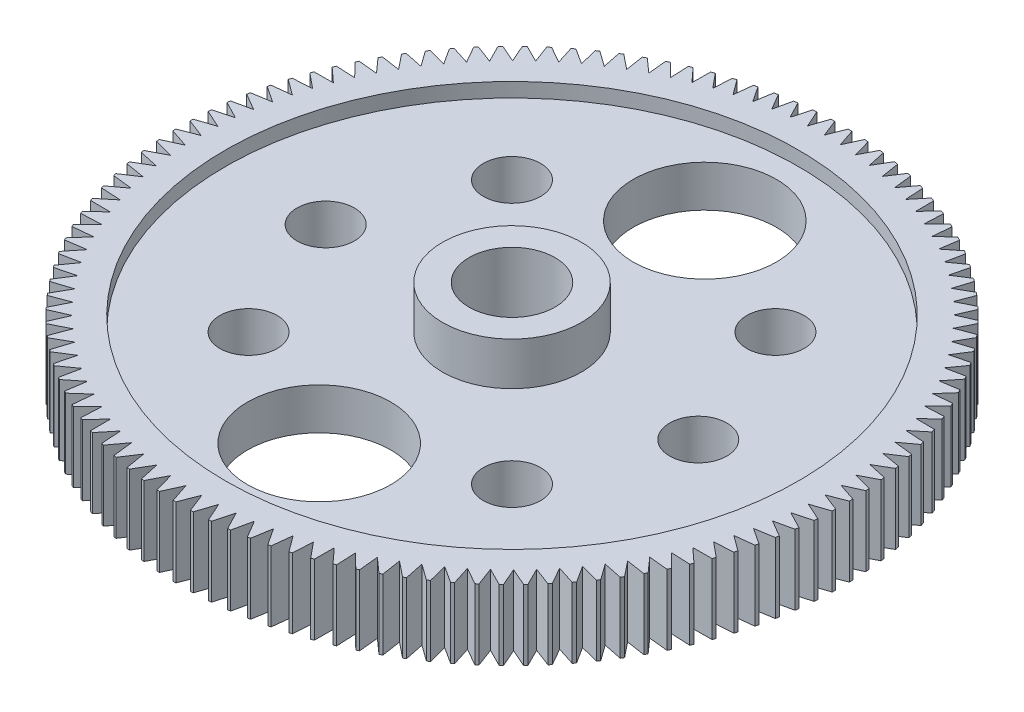
SolidWorks part; units mm, degrees
ref_plane "Спереди" through (0, 0, 0) normal (0, 0, 1) x (1, 0, 0)
ref_plane "Сверху" through (0, 0, 0) normal (0, 1, 0) x (1, 0, 0)
ref_plane "Справа" through (0, 0, 0) normal (1, 0, 0) x (0, 0, -1)
sketch "Эскиз1" plane through (0, 0, 0) normal (0, 1, 0) x (1, 0, 0)
  circle A0 centre (0, 0) radius 23
extrude "Вытянуть1" add sketch "Эскиз1" along normal blind 4.9
sketch "Эскиз2" plane through (0, 4.9, 0) normal (0, 1, 0) x (1, 0, 0)
  line L0 (0, 23) -> (0, 18.1182) construction
  line L1 (-0.5465, 23.1974) -> (0.5465, 23.1974)
  line L2 (0.5465, 23.1974) -> (0, 21.8005)
  line L3 (-0.5465, 23.1974) -> (0, 21.8005)
  line L4 (0.6655, 23.1956) -> (1.757, 23.1384)
  line L5 (1.757, 23.1384) -> (1.1382, 21.772)
  line L6 (0.6655, 23.1956) -> (1.1382, 21.772)
  line L7 (1.8758, 23.1302) -> (2.9628, 23.016)
  line L8 (2.9628, 23.016) -> (2.2733, 21.6839)
  line L9 (1.8758, 23.1302) -> (2.2733, 21.6839)
  line L10 (3.081, 23.0017) -> (4.1605, 22.8307)
  line L11 (4.1605, 22.8307) -> (3.4022, 21.5365)
  line L12 (3.081, 23.0017) -> (3.4022, 21.5365)
  line L13 (4.2778, 22.8102) -> (5.3469, 22.583)
  line L14 (5.3469, 22.583) -> (4.5219, 21.3302)
  line L15 (4.2778, 22.8102) -> (4.5219, 21.3302)
  line L16 (5.463, 22.5564) -> (6.5187, 22.2735)
  line L17 (6.5187, 22.2735) -> (5.6293, 21.0656)
  line L18 (5.463, 22.5564) -> (5.6293, 21.0656)
  line L19 (6.6332, 22.2409) -> (7.6727, 21.9031)
  line L20 (7.6727, 21.9031) -> (6.7213, 20.7434)
  line L21 (6.6332, 22.2409) -> (6.7213, 20.7434)
  line L22 (7.7853, 21.8645) -> (8.8057, 21.4728)
  line L23 (8.8057, 21.4728) -> (7.7949, 20.3646)
  line L24 (7.7853, 21.8645) -> (7.7949, 20.3646)
  line L25 (8.9162, 21.4284) -> (9.9147, 20.9838)
  line L26 (9.9147, 20.9838) -> (8.8473, 19.93)
  line L27 (8.9162, 21.4284) -> (8.8473, 19.93)
  line L28 (10.0227, 20.9337) -> (10.9965, 20.4375)
  line L29 (10.9965, 20.4375) -> (9.8754, 19.441)
  line L30 (10.0227, 20.9337) -> (9.8754, 19.441)
  line L31 (11.1017, 20.3818) -> (12.0483, 19.8353)
  line L32 (12.0483, 19.8353) -> (10.8766, 18.8988)
  line L33 (11.1017, 20.3818) -> (10.8766, 18.8988)
  line L34 (12.1504, 19.7741) -> (13.0671, 19.1788)
  line L35 (13.0671, 19.1788) -> (11.848, 18.3049)
  line L36 (12.1504, 19.7741) -> (11.848, 18.3049)
  line L37 (13.1659, 19.1124) -> (14.0502, 18.47)
  line L38 (14.0502, 18.47) -> (12.787, 17.6611)
  line L39 (13.1659, 19.1124) -> (12.787, 17.6611)
  line L40 (14.1453, 18.3985) -> (14.9948, 17.7106)
  line L41 (14.9948, 17.7106) -> (13.691, 16.969)
  line L42 (14.1453, 18.3985) -> (13.691, 16.969)
  line L43 (15.0861, 17.6343) -> (15.8984, 16.9029)
  line L44 (15.8984, 16.9029) -> (14.5575, 16.2305)
  line L45 (15.0861, 17.6343) -> (14.5575, 16.2305)
  line L46 (15.9855, 16.8219) -> (16.7584, 16.049)
  line L47 (16.7584, 16.049) -> (15.3842, 15.4477)
  line L48 (15.9855, 16.8219) -> (15.3842, 15.4477)
  line L49 (16.8412, 15.9635) -> (17.5726, 15.1512)
  line L50 (17.5726, 15.1512) -> (16.1688, 14.6227)
  line L51 (16.8412, 15.9635) -> (16.1688, 14.6227)
  line L52 (17.6508, 15.0615) -> (18.3387, 14.2121)
  line L53 (18.3387, 14.2121) -> (16.9092, 13.7577)
  line L54 (17.6508, 15.0615) -> (16.9092, 13.7577)
  line L55 (18.4121, 14.1184) -> (19.0546, 13.2341)
  line L56 (19.0546, 13.2341) -> (17.6032, 12.8552)
  line L57 (18.4121, 14.1184) -> (17.6032, 12.8552)
  line L58 (19.123, 13.1367) -> (19.7183, 12.2201)
  line L59 (19.7183, 12.2201) -> (18.2491, 11.9176)
  line L60 (19.123, 13.1367) -> (18.2491, 11.9176)
  line L61 (19.7816, 12.1192) -> (20.3281, 11.1726)
  line L62 (20.3281, 11.1726) -> (18.8451, 10.9475)
  line L63 (19.7816, 12.1192) -> (18.8451, 10.9475)
  line L64 (20.3859, 11.0686) -> (20.8822, 10.0947)
  line L65 (20.8822, 10.0947) -> (19.3894, 9.9475)
  line L66 (20.3859, 11.0686) -> (19.3894, 9.9475)
  line L67 (20.9345, 9.9878) -> (21.3791, 8.9893)
  line L68 (21.3791, 8.9893) -> (19.8807, 8.9204)
  line L69 (20.9345, 9.9878) -> (19.8807, 8.9204)
  line L70 (21.4258, 8.8798) -> (21.8175, 7.8594)
  line L71 (21.8175, 7.8594) -> (20.3175, 7.869)
  line L72 (21.4258, 8.8798) -> (20.3175, 7.869)
  line L73 (21.8584, 7.7476) -> (22.1961, 6.7081)
  line L74 (22.1961, 6.7081) -> (20.6987, 6.7962)
  line L75 (21.8584, 7.7476) -> (20.6987, 6.7962)
  line L76 (22.2311, 6.5943) -> (22.514, 5.5386)
  line L77 (22.514, 5.5386) -> (21.0233, 5.7049)
  line L78 (22.2311, 6.5943) -> (21.0233, 5.7049)
  line L79 (22.543, 5.4231) -> (22.7702, 4.354)
  line L80 (22.7702, 4.354) -> (21.2902, 4.5981)
  line L81 (22.543, 5.4231) -> (21.2902, 4.5981)
  line L82 (22.7931, 4.2372) -> (22.9641, 3.1576)
  line L83 (22.9641, 3.1576) -> (21.4989, 3.4789)
  line L84 (22.7931, 4.2372) -> (21.4989, 3.4789)
  line L85 (22.9809, 3.0398) -> (23.0951, 1.9527)
  line L86 (23.0951, 1.9527) -> (21.6488, 2.3502)
  line L87 (22.9809, 3.0398) -> (21.6488, 2.3502)
  line L88 (23.1057, 1.8342) -> (23.1629, 0.7427)
  line L89 (23.1629, 0.7427) -> (21.7393, 1.2153)
  line L90 (23.1057, 1.8342) -> (21.7393, 1.2153)
  line L91 (23.1672, 0.6237) -> (23.1672, -0.4693)
  line L92 (23.1672, -0.4693) -> (21.7703, 0.0772)
  line L93 (23.1672, 0.6237) -> (21.7703, 0.0772)
  line L94 (23.1654, -0.5883) -> (23.1081, -1.6798)
  line L95 (23.1081, -1.6798) -> (21.7418, -1.061)
  line L96 (23.1654, -0.5883) -> (21.7418, -1.061)
  line L97 (23.1, -1.7986) -> (22.9858, -2.8856)
  line L98 (22.9858, -2.8856) -> (21.6537, -2.1961)
  line L99 (23.1, -1.7986) -> (21.6537, -2.1961)
  line L100 (22.9715, -3.0038) -> (22.8005, -4.0833)
  line L101 (22.8005, -4.0833) -> (21.5063, -3.325)
  line L102 (22.9715, -3.0038) -> (21.5063, -3.325)
  line L103 (22.78, -4.2006) -> (22.5528, -5.2697)
  line L104 (22.5528, -5.2697) -> (21.3, -4.4447)
  line L105 (22.78, -4.2006) -> (21.3, -4.4447)
  line L106 (22.5262, -5.3857) -> (22.2433, -6.4415)
  line L107 (22.2433, -6.4415) -> (21.0354, -5.5521)
  line L108 (22.5262, -5.3857) -> (21.0354, -5.5521)
  line L109 (22.2106, -6.556) -> (21.8729, -7.5955)
  line L110 (21.8729, -7.5955) -> (20.7132, -6.6441)
  line L111 (22.2106, -6.556) -> (20.7132, -6.6441)
  line L112 (21.8343, -7.7081) -> (21.4426, -8.7285)
  line L113 (21.4426, -8.7285) -> (20.3343, -7.7177)
  line L114 (21.8343, -7.7081) -> (20.3343, -7.7177)
  line L115 (21.3982, -8.839) -> (20.9536, -9.8375)
  line L116 (20.9536, -9.8375) -> (19.8998, -8.7701)
  line L117 (21.3982, -8.839) -> (19.8998, -8.7701)
  line L118 (20.9035, -9.9454) -> (20.4073, -10.9193)
  line L119 (20.4073, -10.9193) -> (19.4107, -9.7982)
  line L120 (20.9035, -9.9454) -> (19.4107, -9.7982)
  line L121 (20.3516, -11.0245) -> (19.8051, -11.9711)
  line L122 (19.8051, -11.9711) -> (18.8686, -10.7994)
  line L123 (20.3516, -11.0245) -> (18.8686, -10.7994)
  line L124 (19.7439, -12.0732) -> (19.1486, -12.9899)
  line L125 (19.1486, -12.9899) -> (18.2747, -11.7708)
  line L126 (19.7439, -12.0732) -> (18.2747, -11.7708)
  line L127 (19.0822, -13.0887) -> (18.4398, -13.973)
  line L128 (18.4398, -13.973) -> (17.6309, -12.7097)
  line L129 (19.0822, -13.0887) -> (17.6309, -12.7097)
  line L130 (18.3683, -14.0681) -> (17.6804, -14.9176)
  line L131 (17.6804, -14.9176) -> (16.9388, -13.6138)
  line L132 (18.3683, -14.0681) -> (16.9388, -13.6138)
  line L133 (17.6041, -15.0089) -> (16.8727, -15.8211)
  line L134 (16.8727, -15.8211) -> (16.2003, -14.4803)
  line L135 (17.6041, -15.0089) -> (16.2003, -14.4803)
  line L136 (16.7917, -15.9083) -> (16.0188, -16.6812)
  line L137 (16.0188, -16.6812) -> (15.4175, -15.307)
  line L138 (16.7917, -15.9083) -> (15.4175, -15.307)
  line L139 (15.9333, -16.764) -> (15.121, -17.4954)
  line L140 (15.121, -17.4954) -> (14.5924, -16.0916)
  line L141 (15.9333, -16.764) -> (14.5924, -16.0916)
  line L142 (15.0313, -17.5736) -> (14.1819, -18.2615)
  line L143 (14.1819, -18.2615) -> (13.7275, -16.832)
  line L144 (15.0313, -17.5736) -> (13.7275, -16.832)
  line L145 (14.0882, -18.3349) -> (13.2039, -18.9774)
  line L146 (13.2039, -18.9774) -> (12.825, -17.526)
  line L147 (14.0882, -18.3349) -> (12.825, -17.526)
  line L148 (13.1065, -19.0458) -> (12.1899, -19.6411)
  line L149 (12.1899, -19.6411) -> (11.8874, -18.1719)
  line L150 (13.1065, -19.0458) -> (11.8874, -18.1719)
  line L151 (12.089, -19.7043) -> (11.1424, -20.2509)
  line L152 (11.1424, -20.2509) -> (10.9173, -18.7678)
  line L153 (12.089, -19.7043) -> (10.9173, -18.7678)
  line L154 (11.0384, -20.3087) -> (10.0645, -20.8049)
  line L155 (10.0645, -20.8049) -> (9.9173, -19.3122)
  line L156 (11.0384, -20.3087) -> (9.9173, -19.3122)
  line L157 (9.9576, -20.8573) -> (8.9591, -21.3019)
  line L158 (8.9591, -21.3019) -> (8.8902, -19.8035)
  line L159 (9.9576, -20.8573) -> (8.8902, -19.8035)
  line L160 (8.8496, -21.3486) -> (7.8292, -21.7403)
  line L161 (7.8292, -21.7403) -> (7.8388, -20.2403)
  line L162 (8.8496, -21.3486) -> (7.8388, -20.2403)
  line L163 (7.7174, -21.7811) -> (6.6779, -22.1189)
  line L164 (6.6779, -22.1189) -> (6.766, -20.6215)
  line L165 (7.7174, -21.7811) -> (6.766, -20.6215)
  line L166 (6.5641, -22.1539) -> (5.5084, -22.4368)
  line L167 (5.5084, -22.4368) -> (5.6747, -20.946)
  line L168 (6.5641, -22.1539) -> (5.6747, -20.946)
  line L169 (5.3929, -22.4658) -> (4.3238, -22.693)
  line L170 (4.3238, -22.693) -> (4.5679, -21.213)
  line L171 (5.3929, -22.4658) -> (4.5679, -21.213)
  line L172 (4.207, -22.7159) -> (3.1274, -22.8869)
  line L173 (3.1274, -22.8869) -> (3.4487, -21.4217)
  line L174 (4.207, -22.7159) -> (3.4487, -21.4217)
  line L175 (3.0096, -22.9037) -> (1.9225, -23.0179)
  line L176 (1.9225, -23.0179) -> (2.32, -21.5715)
  line L177 (3.0096, -22.9037) -> (2.32, -21.5715)
  line L178 (1.804, -23.0285) -> (0.7125, -23.0857)
  line L179 (0.7125, -23.0857) -> (1.1851, -21.6621)
  line L180 (1.804, -23.0285) -> (1.1851, -21.6621)
  line L181 (0.5935, -23.09) -> (-0.4995, -23.09)
  line L182 (-0.4995, -23.09) -> (0.047, -21.6931)
  line L183 (0.5935, -23.09) -> (0.047, -21.6931)
  line L184 (-0.6185, -23.0881) -> (-1.71, -23.0309)
  line L185 (-1.71, -23.0309) -> (-1.0912, -21.6646)
  line L186 (-0.6185, -23.0881) -> (-1.0912, -21.6646)
  line L187 (-1.8288, -23.0228) -> (-2.9158, -22.9086)
  line L188 (-2.9158, -22.9086) -> (-2.2263, -21.5764)
  line L189 (-1.8288, -23.0228) -> (-2.2263, -21.5764)
  line L190 (-3.034, -22.8943) -> (-4.1135, -22.7233)
  line L191 (-4.1135, -22.7233) -> (-3.3552, -21.4291)
  line L192 (-3.034, -22.8943) -> (-3.3552, -21.4291)
  line L193 (-4.2308, -22.7028) -> (-5.2999, -22.4755)
  line L194 (-5.2999, -22.4755) -> (-4.4749, -21.2228)
  line L195 (-4.2308, -22.7028) -> (-4.4749, -21.2228)
  line L196 (-5.4159, -22.449) -> (-6.4717, -22.1661)
  line L197 (-6.4717, -22.1661) -> (-5.5823, -20.9582)
  line L198 (-5.4159, -22.449) -> (-5.5823, -20.9582)
  line L199 (-6.5862, -22.1334) -> (-7.6257, -21.7957)
  line L200 (-7.6257, -21.7957) -> (-6.6743, -20.636)
  line L201 (-6.5862, -22.1334) -> (-6.6743, -20.636)
  line L202 (-7.7383, -21.7571) -> (-8.7587, -21.3654)
  line L203 (-8.7587, -21.3654) -> (-7.7479, -20.2571)
  line L204 (-7.7383, -21.7571) -> (-7.7479, -20.2571)
  line L205 (-8.8692, -21.321) -> (-9.8677, -20.8764)
  line L206 (-9.8677, -20.8764) -> (-8.8003, -19.8226)
  line L207 (-8.8692, -21.321) -> (-8.8003, -19.8226)
  line L208 (-9.9756, -20.8263) -> (-10.9495, -20.3301)
  line L209 (-10.9495, -20.3301) -> (-9.8284, -19.3335)
  line L210 (-9.9756, -20.8263) -> (-9.8284, -19.3335)
  line L211 (-11.0547, -20.2744) -> (-12.0013, -19.7278)
  line L212 (-12.0013, -19.7278) -> (-10.8296, -18.7914)
  line L213 (-11.0547, -20.2744) -> (-10.8296, -18.7914)
  line L214 (-12.1034, -19.6667) -> (-13.0201, -19.0714)
  line L215 (-13.0201, -19.0714) -> (-11.801, -18.1975)
  line L216 (-12.1034, -19.6667) -> (-11.801, -18.1975)
  line L217 (-13.1189, -19.005) -> (-14.0032, -18.3625)
  line L218 (-14.0032, -18.3625) -> (-12.74, -17.5537)
  line L219 (-13.1189, -19.005) -> (-12.74, -17.5537)
  line L220 (-14.0983, -18.2911) -> (-14.9478, -17.6032)
  line L221 (-14.9478, -17.6032) -> (-13.644, -16.8615)
  line L222 (-14.0983, -18.2911) -> (-13.644, -16.8615)
  line L223 (-15.0391, -17.5268) -> (-15.8513, -16.7955)
  line L224 (-15.8513, -16.7955) -> (-14.5105, -16.1231)
  line L225 (-15.0391, -17.5268) -> (-14.5105, -16.1231)
  line L226 (-15.9385, -16.7144) -> (-16.7114, -15.9416)
  line L227 (-16.7114, -15.9416) -> (-15.3372, -15.3402)
  line L228 (-15.9385, -16.7144) -> (-15.3372, -15.3402)
  line L229 (-16.7942, -15.8561) -> (-17.5256, -15.0438)
  line L230 (-17.5256, -15.0438) -> (-16.1218, -14.5152)
  line L231 (-16.7942, -15.8561) -> (-16.1218, -14.5152)
  line L232 (-17.6038, -14.9541) -> (-18.2917, -14.1047)
  line L233 (-18.2917, -14.1047) -> (-16.8622, -13.6503)
  line L234 (-17.6038, -14.9541) -> (-16.8622, -13.6503)
  line L235 (-18.3651, -14.011) -> (-19.0076, -13.1267)
  line L236 (-19.0076, -13.1267) -> (-17.5562, -12.7478)
  line L237 (-18.3651, -14.011) -> (-17.5562, -12.7478)
  line L238 (-19.076, -13.0293) -> (-19.6713, -12.1126)
  line L239 (-19.6713, -12.1126) -> (-18.2021, -11.8102)
  line L240 (-19.076, -13.0293) -> (-18.2021, -11.8102)
  line L241 (-19.7346, -12.0118) -> (-20.2811, -11.0652)
  line L242 (-20.2811, -11.0652) -> (-18.7981, -10.8401)
  line L243 (-19.7346, -12.0118) -> (-18.7981, -10.8401)
  line L244 (-20.3389, -10.9612) -> (-20.8352, -9.9873)
  line L245 (-20.8352, -9.9873) -> (-19.3424, -9.8401)
  line L246 (-20.3389, -10.9612) -> (-19.3424, -9.8401)
  line L247 (-20.8875, -9.8804) -> (-21.3321, -8.8819)
  line L248 (-21.3321, -8.8819) -> (-19.8337, -8.813)
  line L249 (-20.8875, -9.8804) -> (-19.8337, -8.813)
  line L250 (-21.3788, -8.7724) -> (-21.7705, -7.752)
  line L251 (-21.7705, -7.752) -> (-20.2705, -7.7616)
  line L252 (-21.3788, -8.7724) -> (-20.2705, -7.7616)
  line L253 (-21.8114, -7.6402) -> (-22.1491, -6.6007)
  line L254 (-22.1491, -6.6007) -> (-20.6517, -6.6888)
  line L255 (-21.8114, -7.6402) -> (-20.6517, -6.6888)
  line L256 (-22.1841, -6.4869) -> (-22.467, -5.4311)
  line L257 (-22.467, -5.4311) -> (-20.9762, -5.5975)
  line L258 (-22.1841, -6.4869) -> (-20.9762, -5.5975)
  line L259 (-22.496, -5.3157) -> (-22.7232, -4.2466)
  line L260 (-22.7232, -4.2466) -> (-21.2432, -4.4907)
  line L261 (-22.496, -5.3157) -> (-21.2432, -4.4907)
  line L262 (-22.7461, -4.1298) -> (-22.9171, -3.0502)
  line L263 (-22.9171, -3.0502) -> (-21.4519, -3.3715)
  line L264 (-22.7461, -4.1298) -> (-21.4519, -3.3715)
  line L265 (-22.9339, -2.9324) -> (-23.0481, -1.8453)
  line L266 (-23.0481, -1.8453) -> (-21.6017, -2.2428)
  line L267 (-22.9339, -2.9324) -> (-21.6017, -2.2428)
  line L268 (-23.0587, -1.7268) -> (-23.1159, -0.6352)
  line L269 (-23.1159, -0.6352) -> (-21.6923, -1.1079)
  line L270 (-23.0587, -1.7268) -> (-21.6923, -1.1079)
  line L271 (-23.1202, -0.5163) -> (-23.1202, 0.5767)
  line L272 (-23.1202, 0.5767) -> (-21.7233, 0.0302)
  line L273 (-23.1202, -0.5163) -> (-21.7233, 0.0302)
  line L274 (-23.1183, 0.6957) -> (-23.0611, 1.7873)
  line L275 (-23.0611, 1.7873) -> (-21.6948, 1.1684)
  line L276 (-23.1183, 0.6957) -> (-21.6948, 1.1684)
  line L277 (-23.053, 1.906) -> (-22.9388, 2.993)
  line L278 (-22.9388, 2.993) -> (-21.6067, 2.3035)
  line L279 (-23.053, 1.906) -> (-21.6067, 2.3035)
  line L280 (-22.9245, 3.1112) -> (-22.7535, 4.1908)
  line L281 (-22.7535, 4.1908) -> (-21.4593, 3.4325)
  line L282 (-22.9245, 3.1112) -> (-21.4593, 3.4325)
  line L283 (-22.733, 4.308) -> (-22.5057, 5.3771)
  line L284 (-22.5057, 5.3771) -> (-21.253, 4.5521)
  line L285 (-22.733, 4.308) -> (-21.253, 4.5521)
  line L286 (-22.4792, 5.4932) -> (-22.1963, 6.5489)
  line L287 (-22.1963, 6.5489) -> (-20.9884, 5.6595)
  line L288 (-22.4792, 5.4932) -> (-20.9884, 5.6595)
  line L289 (-22.1636, 6.6634) -> (-21.8259, 7.7029)
  line L290 (-21.8259, 7.7029) -> (-20.6662, 6.7515)
  line L291 (-22.1636, 6.6634) -> (-20.6662, 6.7515)
  line L292 (-21.7873, 7.8155) -> (-21.3956, 8.836)
  line L293 (-21.3956, 8.836) -> (-20.2873, 7.8251)
  line L294 (-21.7873, 7.8155) -> (-20.2873, 7.8251)
  line L295 (-21.3512, 8.9464) -> (-20.9066, 9.9449)
  line L296 (-20.9066, 9.9449) -> (-19.8528, 8.8775)
  line L297 (-21.3512, 8.9464) -> (-19.8528, 8.8775)
  line L298 (-20.8565, 10.0529) -> (-20.3603, 11.0267)
  line L299 (-20.3603, 11.0267) -> (-19.3637, 9.9056)
  line L300 (-20.8565, 10.0529) -> (-19.3637, 9.9056)
  line L301 (-20.3046, 11.1319) -> (-19.7581, 12.0785)
  line L302 (-19.7581, 12.0785) -> (-18.8216, 10.9068)
  line L303 (-20.3046, 11.1319) -> (-18.8216, 10.9068)
  line L304 (-19.6969, 12.1806) -> (-19.1016, 13.0973)
  line L305 (-19.1016, 13.0973) -> (-18.2277, 11.8782)
  line L306 (-19.6969, 12.1806) -> (-18.2277, 11.8782)
  line L307 (-19.0352, 13.1961) -> (-18.3928, 14.0804)
  line L308 (-18.3928, 14.0804) -> (-17.5839, 12.8172)
  line L309 (-19.0352, 13.1961) -> (-17.5839, 12.8172)
  line L310 (-18.3213, 14.1756) -> (-17.6334, 15.025)
  line L311 (-17.6334, 15.025) -> (-16.8918, 13.7212)
  line L312 (-18.3213, 14.1756) -> (-16.8918, 13.7212)
  line L313 (-17.5571, 15.1163) -> (-16.8257, 15.9286)
  line L314 (-16.8257, 15.9286) -> (-16.1533, 14.5877)
  line L315 (-17.5571, 15.1163) -> (-16.1533, 14.5877)
  line L316 (-16.7446, 16.0157) -> (-15.9718, 16.7886)
  line L317 (-15.9718, 16.7886) -> (-15.3705, 15.4144)
  line L318 (-16.7446, 16.0157) -> (-15.3705, 15.4144)
  line L319 (-15.8863, 16.8714) -> (-15.074, 17.6028)
  line L320 (-15.074, 17.6028) -> (-14.5454, 16.199)
  line L321 (-15.8863, 16.8714) -> (-14.5454, 16.199)
  line L322 (-14.9843, 17.6811) -> (-14.1349, 18.3689)
  line L323 (-14.1349, 18.3689) -> (-13.6805, 16.9394)
  line L324 (-14.9843, 17.6811) -> (-13.6805, 16.9394)
  line L325 (-14.0412, 18.4423) -> (-13.1569, 19.0848)
  line L326 (-13.1569, 19.0848) -> (-12.778, 17.6335)
  line L327 (-14.0412, 18.4423) -> (-12.778, 17.6335)
  line L328 (-13.0595, 19.1532) -> (-12.1428, 19.7485)
  line L329 (-12.1428, 19.7485) -> (-11.8404, 18.2793)
  line L330 (-13.0595, 19.1532) -> (-11.8404, 18.2793)
  line L331 (-12.042, 19.8118) -> (-11.0954, 20.3583)
  line L332 (-11.0954, 20.3583) -> (-10.8703, 18.8753)
  line L333 (-12.042, 19.8118) -> (-10.8703, 18.8753)
  line L334 (-10.9914, 20.4161) -> (-10.0175, 20.9124)
  line L335 (-10.0175, 20.9124) -> (-9.8703, 19.4196)
  line L336 (-10.9914, 20.4161) -> (-9.8703, 19.4196)
  line L337 (-9.9106, 20.9647) -> (-8.9121, 21.4093)
  line L338 (-8.9121, 21.4093) -> (-8.8432, 19.9109)
  line L339 (-9.9106, 20.9647) -> (-8.8432, 19.9109)
  line L340 (-8.8026, 21.456) -> (-7.7822, 21.8477)
  line L341 (-7.7822, 21.8477) -> (-7.7918, 20.3477)
  line L342 (-8.8026, 21.456) -> (-7.7918, 20.3477)
  line L343 (-7.6704, 21.8886) -> (-6.6309, 22.2263)
  line L344 (-6.6309, 22.2263) -> (-6.719, 20.7289)
  line L345 (-7.6704, 21.8886) -> (-6.719, 20.7289)
  line L346 (-6.5171, 22.2613) -> (-5.4614, 22.5442)
  line L347 (-5.4614, 22.5442) -> (-5.6277, 21.0535)
  line L348 (-6.5171, 22.2613) -> (-5.6277, 21.0535)
  line L349 (-5.3459, 22.5732) -> (-4.2768, 22.8004)
  line L350 (-4.2768, 22.8004) -> (-4.5209, 21.3204)
  line L351 (-5.3459, 22.5732) -> (-4.5209, 21.3204)
  line L352 (-4.16, 22.8233) -> (-3.0804, 22.9943)
  line L353 (-3.0804, 22.9943) -> (-3.4017, 21.5291)
  line L354 (-4.16, 22.8233) -> (-3.4017, 21.5291)
  line L355 (-2.9626, 23.0111) -> (-1.8755, 23.1253)
  line L356 (-1.8755, 23.1253) -> (-2.273, 21.679)
  line L357 (-2.9626, 23.0111) -> (-2.273, 21.679)
  line L358 (-1.757, 23.1359) -> (-0.6655, 23.1931)
  line L359 (-0.6655, 23.1931) -> (-1.1381, 21.7695)
  line L360 (-1.757, 23.1359) -> (-1.1381, 21.7695)
  point P8 (0, 23.1974)
  point P13 (1.2113, 23.167)
  point P17 (2.4193, 23.0731)
  point P21 (3.6208, 22.9162)
  point P25 (4.8124, 22.6966)
  point P29 (5.9908, 22.4149)
  point P33 (7.153, 22.072)
  point P37 (8.2955, 21.6687)
  point P41 (9.4154, 21.2061)
  point P45 (10.5096, 20.6856)
  point P49 (11.575, 20.1085)
  point P53 (12.6088, 19.4765)
  point P57 (13.608, 18.7912)
  point P61 (14.5701, 18.0546)
  point P65 (15.4922, 17.2686)
  point P69 (16.372, 16.4354)
  point P73 (17.2069, 15.5574)
  point P77 (17.9948, 14.6368)
  point P81 (18.7334, 13.6763)
  point P85 (19.4207, 12.6784)
  point P89 (20.0548, 11.6459)
  point P93 (20.6341, 10.5817)
  point P97 (21.1568, 9.4886)
  point P101 (21.6216, 8.3696)
  point P105 (22.0272, 7.2279)
  point P109 (22.3726, 6.0665)
  point P113 (22.6566, 4.8886)
  point P117 (22.8786, 3.6974)
  point P121 (23.038, 2.4963)
  point P125 (23.1343, 1.2884)
  point P129 (23.1672, 0.0772)
  point P133 (23.1368, -1.1341)
  point P137 (23.0429, -2.3421)
  point P141 (22.886, -3.5436)
  point P145 (22.6664, -4.7352)
  point P149 (22.3847, -5.9136)
  point P153 (22.0418, -7.0757)
  point P157 (21.6385, -8.2183)
  point P161 (21.1759, -9.3382)
  point P165 (20.6554, -10.4324)
  point P169 (20.0783, -11.4978)
  point P173 (19.4463, -12.5316)
  point P177 (18.761, -13.5308)
  point P181 (18.0244, -14.4928)
  point P185 (17.2384, -15.415)
  point P189 (16.4052, -16.2948)
  point P193 (15.5272, -17.1297)
  point P197 (14.6066, -17.9176)
  point P201 (13.6461, -18.6561)
  point P205 (12.6482, -19.3435)
  point P209 (11.6157, -19.9776)
  point P213 (10.5515, -20.5568)
  point P217 (9.4584, -21.0796)
  point P221 (8.3394, -21.5444)
  point P225 (7.1977, -21.95)
  point P229 (6.0362, -22.2953)
  point P233 (4.8583, -22.5794)
  point P237 (3.6672, -22.8014)
  point P241 (2.4661, -22.9608)
  point P245 (1.2582, -23.0571)
  point P249 (0.047, -23.09)
  point P253 (-1.1643, -23.0595)
  point P257 (-2.3723, -22.9657)
  point P261 (-3.5738, -22.8088)
  point P265 (-4.7654, -22.5892)
  point P269 (-5.9438, -22.3075)
  point P273 (-7.106, -21.9646)
  point P277 (-8.2485, -21.5612)
  point P281 (-9.3684, -21.0987)
  point P285 (-10.4626, -20.5782)
  point P289 (-11.528, -20.0011)
  point P293 (-12.5618, -19.3691)
  point P297 (-13.561, -18.6838)
  point P301 (-14.5231, -17.9471)
  point P305 (-15.4452, -17.1612)
  point P309 (-16.325, -16.328)
  point P313 (-17.1599, -15.4499)
  point P317 (-17.9478, -14.5294)
  point P321 (-18.6864, -13.5688)
  point P325 (-19.3737, -12.571)
  point P329 (-20.0078, -11.5385)
  point P333 (-20.587, -10.4743)
  point P337 (-21.1098, -9.3812)
  point P341 (-21.5746, -8.2622)
  point P345 (-21.9802, -7.1204)
  point P349 (-22.3255, -5.959)
  point P353 (-22.6096, -4.7811)
  point P357 (-22.8316, -3.59)
  point P361 (-22.991, -2.3888)
  point P365 (-23.0873, -1.181)
  point P369 (-23.1202, 0.0302)
  point P373 (-23.0897, 1.2415)
  point P377 (-22.9959, 2.4495)
  point P381 (-22.839, 3.651)
  point P385 (-22.6194, 4.8426)
  point P389 (-22.3377, 6.021)
  point P393 (-21.9948, 7.1832)
  point P397 (-21.5915, 8.3257)
  point P401 (-21.1289, 9.4456)
  point P405 (-20.6084, 10.5398)
  point P409 (-20.0313, 11.6052)
  point P413 (-19.3993, 12.639)
  point P417 (-18.714, 13.6382)
  point P421 (-17.9773, 14.6003)
  point P425 (-17.1914, 15.5224)
  point P429 (-16.3582, 16.4022)
  point P433 (-15.4801, 17.2371)
  point P437 (-14.5596, 18.025)
  point P441 (-13.5991, 18.7636)
  point P445 (-12.6012, 19.4509)
  point P449 (-11.5687, 20.085)
  point P453 (-10.5045, 20.6643)
  point P457 (-9.4114, 21.187)
  point P461 (-8.2924, 21.6518)
  point P465 (-7.1507, 22.0574)
  point P469 (-5.9892, 22.4028)
  point P473 (-4.8113, 22.6868)
  point P477 (-3.6202, 22.9088)
  point P481 (-2.4191, 23.0682)
  point P485 (-1.2112, 23.1645)
extrude "Вытянуть2" cut sketch "Эскиз2" against normal blind 4.9
sketch "Эскиз3" plane through (0, 4.9, 0) normal (0, 1, 0) x (1, 0, 0)
  circle A0 centre (0, 0) radius 20
extrude "Вытянуть3" cut sketch "Эскиз3" against normal blind 1
sketch "Эскиз4" plane through (0, 0, 0) normal (0, -1, 0) x (1, 0, 0)
  circle A0 centre (0, 0) radius 20
extrude "Вытянуть4" cut sketch "Эскиз4" against normal blind 1
sketch "Эскиз5" plane through (0, 3.9, 0) normal (0, 1, 0) x (1, 0, 0)
  circle A0 centre (0, 0) radius 3
extrude "Вытянуть5" cut sketch "Эскиз5" against normal through all
sketch "Эскиз6" plane through (0, 3.9, 0) normal (0, 1, 0) x (1, 0, 0)
  circle A0 centre (0, 0) radius 3
  circle A1 centre (0, 0) radius 4.85
extrude "Вытянуть6" add sketch "Эскиз6" along normal blind 3
sketch "Эскиз7" plane through (0, 1, 0) normal (0, -1, 0) x (1, 0, 0)
  circle A0 centre (0, 0) radius 3
  circle A1 centre (0, 0) radius 4.85
extrude "Вытянуть7" add sketch "Эскиз7" along normal blind 3
sketch "Эскиз8" plane through (0, 1, 0) normal (0, -1, 0) x (1, 0, 0)
  line L0 (0.1421, 0) -> (44.3302, 0) construction
  line L1 (0, 0) -> (0, 25.1722) construction
  line L2 (0.6566, -0.6566) -> (-20.5771, 20.5771) construction
  circle A0 centre (0, 13.4574) radius 5
  circle A1 centre (0, -13.4574) radius 5
  circle A2 centre (-13, 0) radius 2
  circle A3 centre (13, 0) radius 2
  circle A4 centre (-9.1924, 9.1924) radius 2
  circle A5 centre (9.1924, -9.1924) radius 2
  circle A6 centre (9.1924, 9.1924) radius 2
  circle A7 centre (-9.1924, -9.1924) radius 2
  dimension "D1" = 45
  dimension "D3" = 13
  dimension "D2" = 13
  dimension "D4" = 13
extrude "Вытянуть8" cut sketch "Эскиз8" against normal through all
